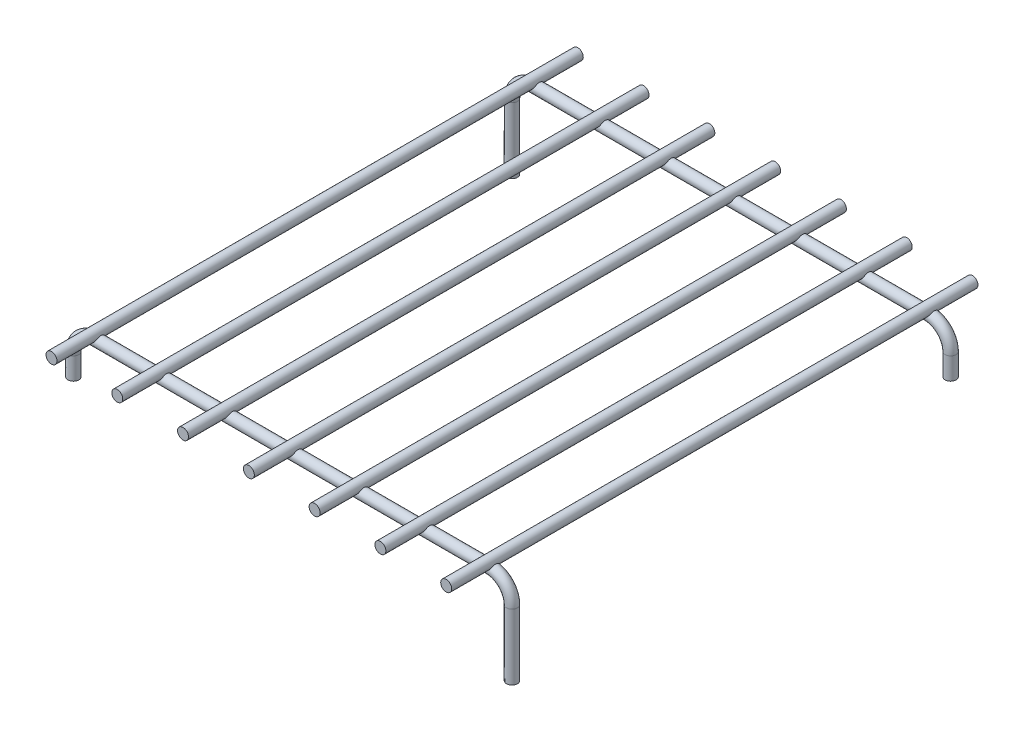
SolidWorks part; units mm, degrees
material "Galvanized Steel"
ref_plane "Front Plane" through (0, 0, 0) normal (0, 0, 1) x (1, 0, 0)
ref_plane "Top Plane" through (0, 0, 0) normal (0, 1, 0) x (1, 0, 0)
ref_plane "Right Plane" through (0, 0, 0) normal (1, 0, 0) x (0, 0, -1)
sketch "Sketch1" plane through (0, 0, 0) normal (0, 0, 1) x (1, 0, 0)
  line L0 (-63.5, -12.7) -> (-63.5, -6.35)
  line L1 (-57.15, 0) -> (57.15, 0)
  line L2 (0, 0) -> (0, 37.1689) construction
  line L3 (63.5, -6.35) -> (63.5, -25.4)
  arc A0 (-63.5, -6.35) -> (-57.15, 0) centre (-57.15, -6.35) cw
  arc A1 (63.5, -6.35) -> (57.15, 0) centre (57.15, -6.35) ccw
  dimension "D1" = 6.35
  dimension "D2" = 127
  dimension "D3" = 12.7
  dimension "D4" = 12.7
ref_plane "Plane1" through (-63.5, -12.7, 0) normal (0, 1, 0) x (-1, 0, 0)
sketch "Sketch2" plane through (-63.5, -12.7, 0) normal (0, 1, 0) x (-1, 0, 0)
  circle A0 centre (0, 0) radius 1.5875
  dimension "D1" = 3.175
sweep "Sweep1" add profiles "Sketch2" path "Sketch1"
ref_axis "Axis1" through (0, 0, -80.9) along (0, 0, 1)
pattern_linear "LPattern1" count 2 spacing 127 along (0, 0, -1) of bodies 101
sketch "Sketch3" plane through (0, 0, 0) normal (0, 0, 1) x (1, 0, 0)
  line L0 (57.15, 1.5875) -> (-57.15, 1.5875) construction
  circle A0 centre (0, 1.5875) radius 1.5875
  dimension "D1" = 3.175
extrude "Extrude1" add sketch "Sketch3" along normal blind 12.7 and the other way blind 139.7 separate body
ref_axis "Axis2" through (-80.9, 0, 0) along (1, 0, 0)
pattern_linear "LPattern2" count 4 spacing 19.05 along (1, 0, 0) count 4 spacing 19.05 along (-1, 0, 0) of bodies 103
combine bodies "Combine1" operation type add bodies to combine 101 102 103 104 105 106 107 108 109
sketch "Sketch4" plane through (0, -12.7, 0) normal (0, -1, 0) x (1, 0, 0)
  circle A1 centre (-63.5, -127) radius 1.5875
  circle A2 centre (-63.5, -127) radius 1.5875
  dimension "D1" = 0
extrude "Extrude2" add sketch "Sketch4" along normal up to surface (12.7 mm away) up to face at (65.0875, -25.4, 0)
sketch "Sketch5" plane through (0, -25.4, 0) normal (0, -1, 0) x (1, 0, 0)
  circle A1 centre (63.5, -127) radius 1.5875
  circle A2 centre (63.5, -127) radius 1.5875
  dimension "D1" = 0
extrude "Cut-Extrude1" cut sketch "Sketch5" against normal up to surface (12.7 mm away) up to face at (-65.0875, -12.7, 0)
